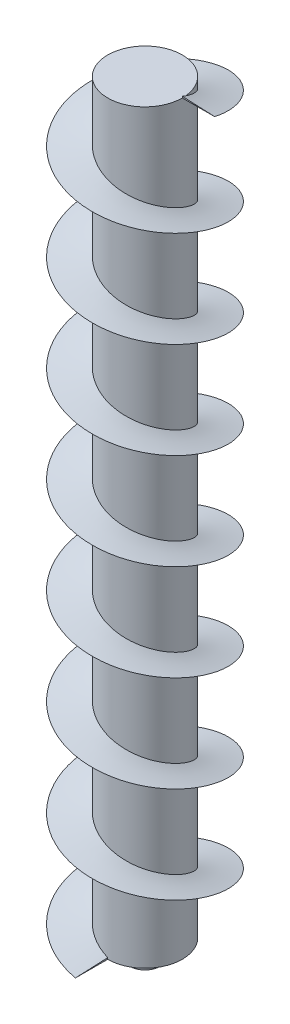
SolidWorks part; units mm, degrees
ref_plane "前基準面" through (0, 0, 0) normal (0, 0, 1) x (1, 0, 0)
ref_plane "上基準面" through (0, 0, 0) normal (0, 1, 0) x (1, 0, 0)
ref_plane "右基準面" through (0, 0, 0) normal (1, 0, 0) x (0, 0, -1)
sketch "草圖1" plane through (0, 0, 0) normal (0, 1, 0) x (1, 0, 0)
  circle A0 centre (0, 0) radius 7.5
  dimension "D1" = 15
extrude "填料-伸長1" add sketch "草圖1" along normal blind 150 contours A0
sketch "草圖2" plane through (0, 0, 0) normal (0, -1, 0) x (1, 0, 0)
  circle A1 centre (0, 0) radius 7.5
  circle A2 centre (0, 0) radius 7.5
  dimension "D1" = 0
curve "螺旋曲線/渦捲線1" pitch 19.3548 height 150 turns 7.75
sketch "草圖4" plane through (0, 0, 0) normal (1, 0, 0) x (0, 0, -1)
  line L0 (-7.5, 0.3) -> (-14, 0)
  line L1 (-7.5, 0) -> (-14, 0)
  line L2 (-7.5, 0) -> (-7.5, 0.3)
  dimension "D1" = 0.3
  dimension "D2" = 6.5
sweep "掃出2" add profiles "草圖4" path "螺旋曲線/渦捲線1"
sketch "草圖8" plane through (0, 0, 0) normal (0, -1, 0) x (1, 0, 0)
  circle A0 centre (0, 0) radius 3
  dimension "D1" = 6
extrude "填料-伸長2" add sketch "草圖8" along normal blind 5
sketch "草圖9" plane through (0, -5, 0) normal (0, -1, 0) x (1, 0, 0)
  circle A1 centre (0, 0) radius 3
  circle A2 centre (0, 0) radius 3
  dimension "D1" = 0
extrude "除料-伸長1" cut sketch "草圖9" against normal blind 1.5
